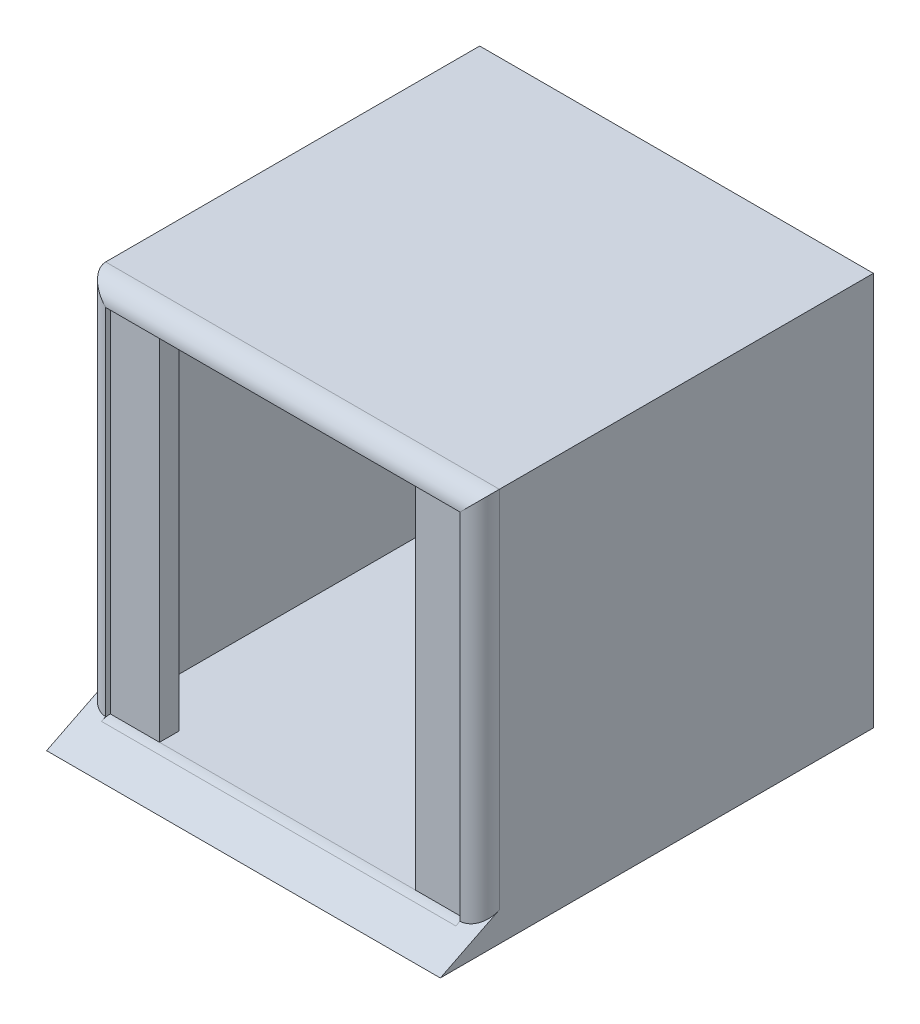
SolidWorks part; units mm, degrees
ref_plane "Front Plane" through (0, 0, 0) normal (0, 0, 1) x (1, 0, 0)
ref_plane "Top Plane" through (0, 0, 0) normal (0, 1, 0) x (1, 0, 0)
ref_plane "Right Plane" through (0, 0, 0) normal (1, 0, 0) x (0, 0, -1)
sketch "Sketch1" plane through (0, 0, 0) normal (0, 1, 0) x (1, 0, 0)
  line L1 (0, 0) -> (2000, 0)
  line L2 (0, 0) -> (0, 2000)
  line L3 (0, 2000) -> (2000, 2000)
  line L4 (2000, 0) -> (2000, 2000)
  dimension "D1" = 2000
  dimension "D2" = 2000
extrude "Boss-Extrude1" add sketch "Sketch1" along normal blind 2000
shell "Shell3" thickness 100 removed face at (1000, 1000, 0)
sketch "Sketch2" plane through (0, 0, 0) normal (1, 0, 0) x (0, 0, -1)
  line L0 (0, 100) -> (-200, 0)
  line L1 (-200, 0) -> (0, 0)
  line L2 (0, 0) -> (0, 100)
  dimension "D1" = 200
extrude "Boss-Extrude2" add sketch "Sketch2" along normal blind 2000
fillet "Fillet1" radius 100 4 edges at (0, 1050, 0) (2000, 1050, 0) (1000, 2000, 0) (1000, 100, 0)
sketch "Sketch3" plane through (0, 100, 0) normal (0, 1, 0) x (1, 0, 0)
  line L0 (1650, 23.6068) -> (1650, 123.6068)
  line L1 (100, 23.6068) -> (350, 23.6068)
  line L2 (100, 23.6068) -> (100, 123.6068)
  line L3 (100, 123.6068) -> (350, 123.6068)
  line L4 (350, 23.6068) -> (350, 123.6068)
  line L5 (1650, 23.6068) -> (1900, 23.6068)
  line L6 (1900, 23.6068) -> (1900, 123.6068)
  line L7 (1650, 123.6068) -> (1900, 123.6068)
  dimension "D1" = 100
  dimension "D2" = 250
  dimension "D3" = 2
extrude "Boss-Extrude3" add sketch "Sketch3" along normal up to surface (1800 mm away) up to face at (1000, 1900, -950)
